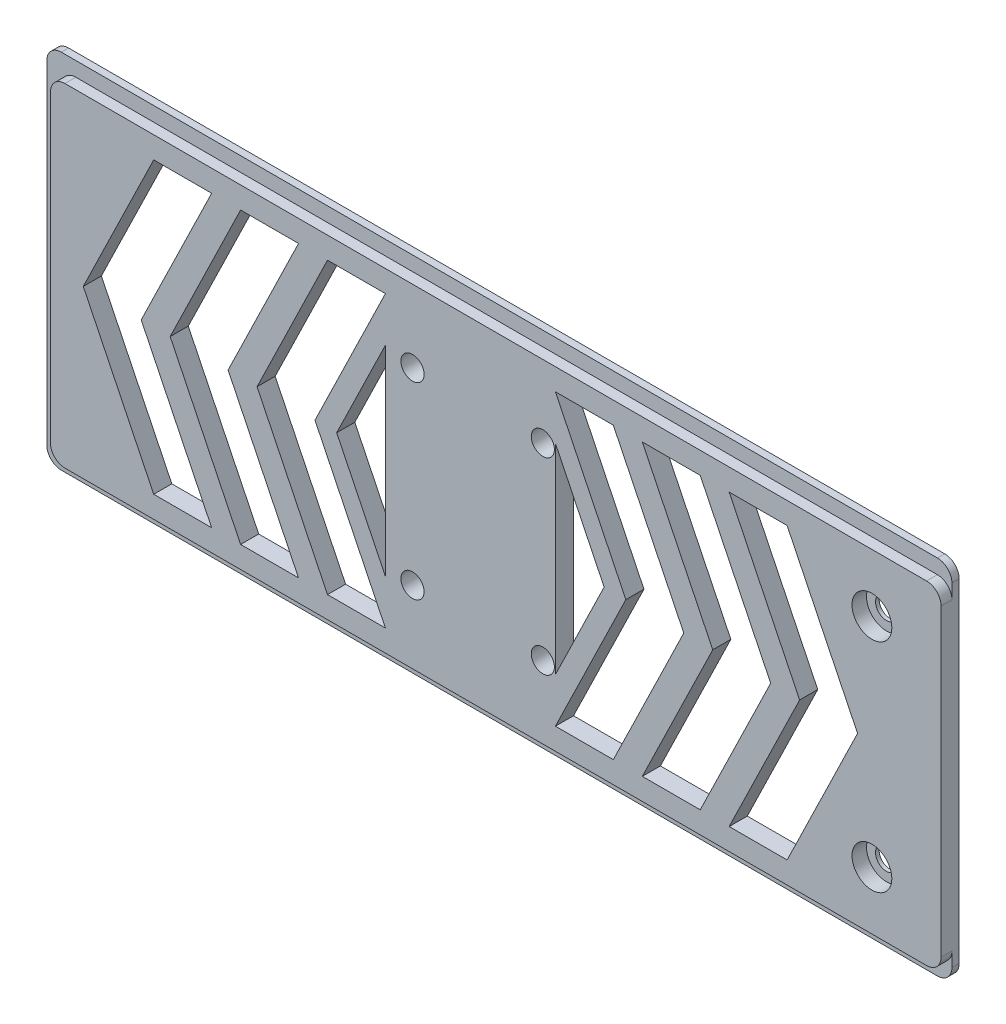
SolidWorks part; units mm, degrees
ref_plane "Plano frontal" through (0, 0, 0) normal (0, 0, 1) x (1, 0, 0)
ref_plane "Plano superior" through (0, 0, 0) normal (0, 1, 0) x (1, 0, 0)
ref_plane "Plano direito" through (0, 0, 0) normal (1, 0, 0) x (0, 0, -1)
other "Centro da massa"
sketch "Esboço1" plane through (0, 0, 0) normal (0, 0, 1) x (1, 0, 0)
  line L1 (-17.8424, 34.9053) -> (107.1576, 34.9053)
  line L2 (-17.8424, 34.9053) -> (-17.8424, -15.0947)
  line L3 (-17.8424, -15.0947) -> (107.1576, -15.0947)
  line L4 (107.1576, 34.9053) -> (107.1576, -15.0947)
  dimension "D1" = 50
  dimension "D2" = 125
extrude "Ressalto-extrusão1" add sketch "Esboço1" along normal blind 2.5
sketch "Esboço2" plane through (0, 0, 2.5) normal (0, 0, 1) x (1, 0, 0)
  line L1 (31.1576, 25.9053) -> (55.1576, 25.9053)
  line L2 (31.1576, 25.9053) -> (31.1576, -6.0947)
  line L3 (31.1576, -6.0947) -> (55.1576, -6.0947)
  line L4 (55.1576, 25.9053) -> (55.1576, -6.0947)
  line L8 (107.1576, -15.0947) -> (107.1576, 34.9053) construction
  line L9 (-17.8424, -15.0947) -> (107.1576, -15.0947) construction
  line L10 (43.1576, 25.9053) -> (43.1576, -6.0947) construction
  line L11 (31.1576, 9.9053) -> (43.1576, 9.9053) construction
  line L12 (55.1576, 25.9053) -> (107.1576, 25.9053) construction
  line L15 (55.1576, 25.9053) -> (55.1576, 34.9053) construction
  line L16 (107.1576, 34.9053) -> (-17.8424, 34.9053) construction
  line L17 (55.1576, -6.0947) -> (55.1576, -15.0947) construction
  circle A0 centre (34.1576, 22.9053) radius 1.6
  circle A1 centre (34.1576, -3.0947) radius 1.6
  circle A2 centre (52.1576, -3.0947) radius 1.6
  circle A3 centre (52.1576, 22.9053) radius 1.6
  dimension "D5" = 3
  dimension "D1" = 24
  dimension "D2" = 32
  dimension "D3" = 52
  dimension "D6" = 3
extrude "Corte-extrusão2" cut sketch "Esboço2" against normal blind 2.5 contours A2 | A1 | A3 | A0
sketch "Esboço3" plane through (0, 0, 2.5) normal (0, 0, 1) x (1, 0, 0)
  line L0 (-17.8424, 9.9053) -> (107.1576, 9.9053) construction
  line L1 (-17.8424, 34.9053) -> (-17.8424, -15.0947) construction
  line L2 (107.1576, -15.0947) -> (107.1576, 34.9053) construction
  line L4 (-17.8424, 34.9053) -> (107.1576, 34.9053)
  line L5 (-17.8424, 34.9053) -> (-17.8424, 32.9053)
  line L6 (-15.8424, 32.9053) -> (107.1576, 32.9053)
  line L7 (107.1576, 34.9053) -> (107.1576, 32.9053)
  line L8 (107.1576, -15.0947) -> (107.1576, -13.0947)
  line L9 (-17.8424, -15.0947) -> (107.1576, -15.0947)
  line L10 (-17.8424, -15.0947) -> (-17.8424, -13.0947)
  line L11 (-17.8424, 32.9053) -> (-17.8424, -13.0947)
  line L12 (-17.8424, 34.9053) -> (-15.8424, 34.9053)
  line L13 (-17.8424, 34.9053) -> (-17.8424, -15.0947)
  line L14 (-17.8424, -15.0947) -> (-15.8424, -15.0947)
  line L15 (-15.8424, 32.9053) -> (-15.8424, -13.0947)
  line L16 (-15.8424, -13.0947) -> (107.1576, -13.0947)
  point P18 (-15.8424, 32.9053)
  line M17 (-17.8424, 34.9053) -> (-17.8424, -15.0947)
  line M18 (-17.8424, -15.0947) -> (107.1576, -15.0947)
  line M19 (107.1576, -15.0947) -> (107.1576, 34.9053)
  line M20 (107.1576, 34.9053) -> (-17.8424, 34.9053)
  dimension "D1" = 2
  dimension "D2" = 2
extrude "Corte-extrusão3" cut sketch "Esboço3" against normal blind 1.5 contours L0 L15 L6 L4 M17 M19 M20 | L0 L13 L9 L16 L15 M17 M18 M19 region at (-16.5677, 21.4053, 2.5) region at (-16.8424, 8.6306, 2.5)
sketch "Esboço4" plane through (0, 0, 2.5) normal (0, 0, 1) x (1, 0, 0)
  line L0 (42.1576, 32.9053) -> (42.1576, -13.0947) construction
  line L5 (0.6906, 9.9053) -> (10.4196, -10.0947)
  line L6 (18.4196, -10.0947) -> (10.4196, -10.0947)
  line L7 (20.6906, 9.9053) -> (30.4196, 29.9053)
  line L16 (20.6906, 9.9053) -> (30.4196, -10.0947)
  line L18 (12.6906, 9.9053) -> (22.4196, 29.9053)
  line L19 (22.4196, 29.9053) -> (30.4196, 29.9053)
  line L20 (30.4196, 23.7382) -> (23.6906, 9.9053)
  line L21 (23.6906, 9.9053) -> (30.4196, -3.9275)
  line L24 (-15.8424, 32.9053) -> (-15.8424, -13.0947) construction
  line L38 (-12.9532, 9.9053) -> (-11.3094, 9.9053) construction
  line L50 (30.4196, 23.7382) -> (30.4196, -3.9275)
  line L51 (30.4196, -3.9275) -> (30.4196, 23.7382)
  line L53 (12.6906, 9.9053) -> (22.4196, -10.0947)
  line L55 (30.4196, -10.0947) -> (22.4196, -10.0947)
  line L87 (8.6906, 9.9053) -> (18.4196, -10.0947)
  line L88 (8.6906, 9.9053) -> (18.4196, 29.9053)
  line L89 (95.6245, 9.9053) -> (105.5606, 9.9053) construction
  line L90 (10.4196, 29.9053) -> (18.4196, 29.9053)
  line L91 (0.6906, 9.9053) -> (10.4196, 29.9053)
  line L92 (-11.3094, 9.9053) -> (-1.5804, -10.0947)
  line L93 (6.4196, -10.0947) -> (-1.5804, -10.0947)
  line L94 (-3.3094, 9.9053) -> (6.4196, -10.0947)
  line L95 (-3.3094, 9.9053) -> (6.4196, 29.9053)
  line L96 (-1.5804, 29.9053) -> (6.4196, 29.9053)
  line L97 (-11.3094, 9.9053) -> (-1.5804, 29.9053)
  line L98 (95.6245, 9.9053) -> (85.8956, 29.9053)
  line L99 (85.8956, 29.9053) -> (77.8956, 29.9053)
  line L100 (87.6245, 9.9053) -> (77.8956, 29.9053)
  line L101 (87.6245, 9.9053) -> (77.8956, -10.0947)
  line L102 (77.8956, -10.0947) -> (85.8956, -10.0947)
  line L103 (95.6245, 9.9053) -> (85.8956, -10.0947)
  line L104 (83.6245, 9.9053) -> (73.8956, 29.9053)
  line L105 (73.8956, 29.9053) -> (65.8956, 29.9053)
  line L106 (75.6245, 9.9053) -> (65.8956, 29.9053)
  line L107 (75.6245, 9.9053) -> (65.8956, -10.0947)
  line L108 (65.8956, -10.0947) -> (73.8956, -10.0947)
  line L109 (83.6245, 9.9053) -> (73.8956, -10.0947)
  line L110 (71.6245, 9.9053) -> (61.8956, 29.9053)
  line L111 (61.8956, 29.9053) -> (53.8956, 29.9053)
  line L112 (63.6245, 9.9053) -> (53.8956, 29.9053)
  line L113 (63.6245, 9.9053) -> (53.8956, -10.0947)
  line L114 (53.8956, -10.0947) -> (61.8956, -10.0947)
  line L115 (71.6245, 9.9053) -> (61.8956, -10.0947)
  line L116 (60.6245, 9.9053) -> (53.8956, -3.9275)
  line L117 (53.8956, 23.7382) -> (60.6245, 9.9053)
  line L118 (53.8956, -3.9275) -> (53.8956, 23.7382)
  dimension "D3" = 58
  dimension "D1" = 40
  dimension "D2" = 3
  dimension "D4" = 8
  dimension "D5" = 8
  dimension "D6" = 3
extrude "Corte-extrusão5" cut sketch "Esboço4" against normal through all both and the other way through all contours L97 L92 L93 L94 L95 L96 | L91 L5 L6 L87 L88 L90 | L55 L16 L7 L19 L18 L53 | L50 L20 L21 | L118 L116 L117 | L115 L110 L111 L112 L113 L114 | L109 L104 L105 L106 L107 L108 | L103 L98 L99 L100 L101 L102
sketch "Esboço12" plane through (0, 0, 2.5) normal (0, 0, 1) x (1, 0, 0)
  line L0 (107.1576, -13.0947) -> (107.1576, 32.9053) construction
  line L1 (-15.8424, 32.9053) -> (107.1576, 32.9053) construction
  line L2 (95.6245, 9.9053) -> (107.1576, 9.9053) construction
  circle A0 centre (97.6076, 24.9053) radius 2.75
  circle A1 centre (97.6076, -5.0947) radius 2.75
  point P0 (97.6076, 24.9053)
  point P8 (97.6076, -5.0947)
  point P13 (94.8576, 24.9053)
  point P14 (94.8576, -5.0947)
  dimension "D3" = 5.5
  dimension "D4" = 5.5
  dimension "D1" = 12.3
  dimension "D2" = 8
extrude "Corte-extrusão6" cut sketch "Esboço12" against normal blind 2
sketch "Esboço19" plane through (0, 0, 0.5) normal (0, 0, 1) x (1, 0, 0)
  circle A0 centre (97.6076, 24.9053) radius 1.5
  circle A1 centre (97.6076, -5.0947) radius 1.5
extrude "Corte-extrusão7" cut sketch "Esboço19" against normal blind 2
fillet "Filete1" radius 2 8 edges at (-17.8424, -15.0947, 0.5) (-15.8424, -13.0947, 1.75) (-17.8424, 34.9053, 0.5) (-15.8424, 32.9053, 1.75) (107.1576, -15.0947, 0.5) (107.1576, -13.0947, 1.75) (107.1576, 32.9053, 1.75) (107.1576, 34.9053, 0.5)
